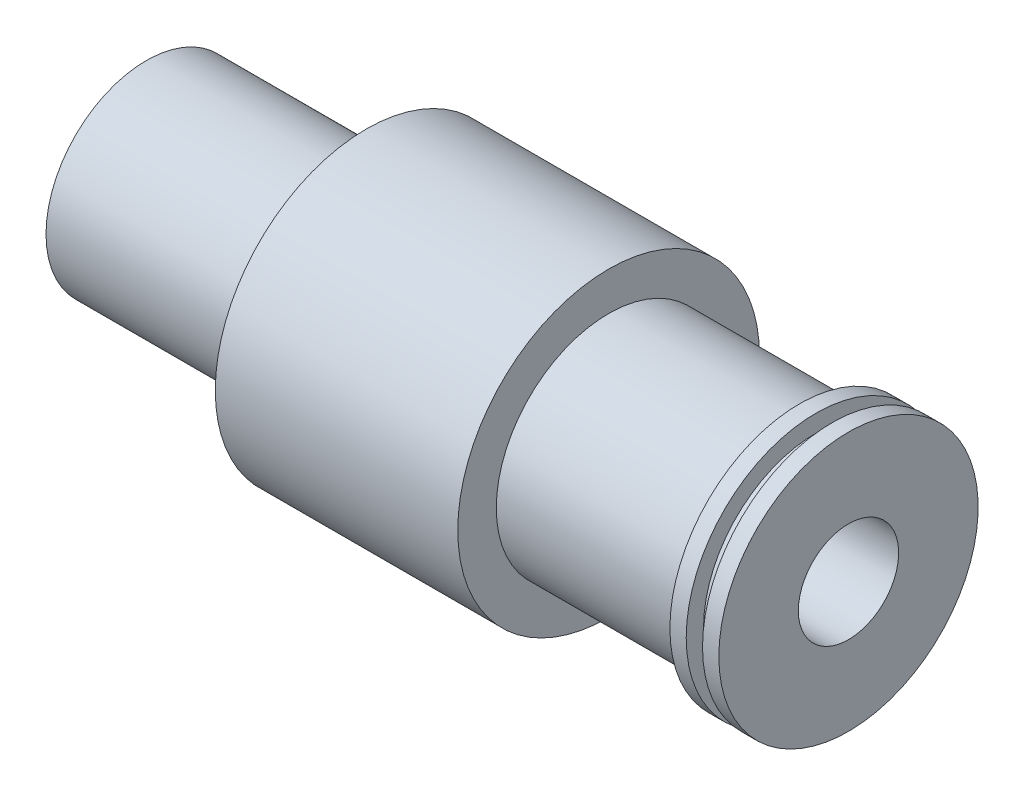
SolidWorks part; units mm, degrees
material "Chrome Stainless Steel"
ref_plane "Front" through (0, 0, 0) normal (0, 0, 1) x (1, 0, 0)
ref_plane "Top" through (0, 0, 0) normal (0, 1, 0) x (1, 0, 0)
ref_plane "Right" through (0, 0, 0) normal (1, 0, 0) x (0, 0, -1)
ref_axis "Axis1" through (0, 0, 55) along (0, 0, -1)
sketch "Sketch1" plane through (0, 0, 0) normal (0, 0, 1) x (1, 0, 0)
  line L0 (-11.1125, 0) -> (11.1125, 0) construction
  line L1 (-11.1125, 1.5875) -> (-11.1125, 3.175)
  line L2 (-11.1125, 3.175) -> (-4.1542, 3.175)
  line L3 (-4.1542, 3.175) -> (-4.1542, 4.7752)
  line L4 (-4.1542, 4.7752) -> (3.5205, 4.7752)
  line L5 (3.5205, 4.7752) -> (3.5205, 3.556)
  line L6 (3.5205, 3.556) -> (9.5635, 3.556)
  line L7 (9.5635, 3.556) -> (9.5635, 4.1041)
  line L8 (9.5635, 4.1041) -> (10.0798, 4.1041)
  line L9 (10.0798, 4.1041) -> (10.0798, 3.556)
  line L10 (10.0798, 3.556) -> (10.5962, 3.556)
  line L11 (10.5962, 3.556) -> (10.5962, 4.1041)
  line L12 (10.5962, 4.1041) -> (11.1125, 4.1041)
  line L13 (11.1125, 4.1041) -> (11.1125, 1.5875)
  line L14 (-11.1125, 1.5875) -> (11.1125, 1.5875)
  line L15 (11.1125, 0) -> (11.1125, 1.5875) construction
  line L16 (-11.1125, 1.5875) -> (-11.1125, 0) construction
  point P4 (0, 0)
  dimension "D1" = 22.225
  dimension "D2" = 3.175
  dimension "D3" = 4.7752
  dimension "D4" = 3.556
  dimension "D5" = 4.1542
  dimension "D6" = 3.5205
  dimension "D7" = 1.5875
  dimension "D8" = 0.5481
  dimension "D9" = 0.5163
  dimension "D10" = 1.0327
revolve "Revolve1" add sketch "Sketch1" angle 360 about L0
